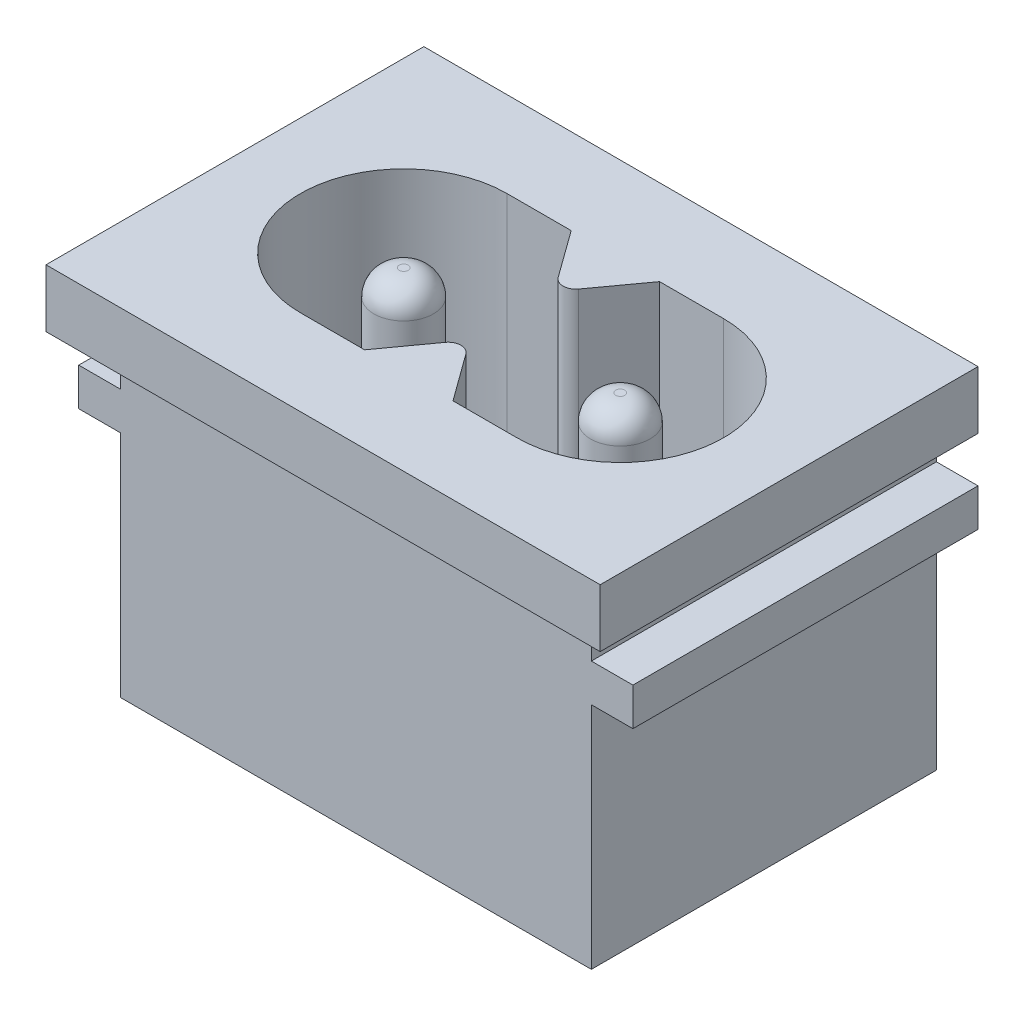
SolidWorks part; units mm, degrees
ref_plane "前视基准面" through (0, 0, 0) normal (0, 0, 1) x (1, 0, 0)
ref_plane "上视基准面" through (0, 0, 0) normal (0, 1, 0) x (1, 0, 0)
ref_plane "右视基准面" through (0, 0, 0) normal (1, 0, 0) x (0, 0, -1)
sketch "草图1" plane through (0, 0, 0) normal (0, 1, 0) x (1, 0, 0)
  line L0 (0, 0) -> (-50000, 0) construction
  line L1 (11, -7.5) -> (-11, -7.5)
  line L2 (11, -7.5) -> (11, 7.5)
  line L3 (11, 7.5) -> (-11, 7.5)
  line L4 (-11, -7.5) -> (-11, 7.5)
  line L5 (11, -7.5) -> (-11, 7.5) construction
  line L6 (11, 7.5) -> (-11, -7.5) construction
  line L7 (0, 0) -> (0, -50000) construction
  point P0 (0, 0)
  dimension "D1" = 22
  dimension "D2" = 15
extrude "凸台-拉伸1" add sketch "草图1" along normal blind 2.3
sketch "草图2" plane through (0, 0, 0) normal (0, -1, 0) x (1, 0, 0)
  line L0 (11, -7.5) -> (-11, -7.5) construction
  line L1 (-9.35, -7.5) -> (9.35, -7.5)
  line L2 (-9.35, -7.5) -> (-9.35, 6.2)
  line L3 (-9.35, 6.2) -> (9.35, 6.2)
  line L4 (9.35, -7.5) -> (9.35, 6.2)
  line L5 (0, 7.5) -> (0, -49992.5) construction
  line L6 (-11, 7.5) -> (11, 7.5) construction
  point P10 (0, 7.5)
  dimension "D1" = 13.7
  dimension "D2" = 18.7
  dimension "D3" = 9.35
extrude "凸台-拉伸2" add sketch "草图2" along normal blind 12.4
sketch "草图3" plane through (-9.35, 0, 0) normal (-1, 0, 0) x (0, 0, 1)
  line L0 (-7.5, -12.4) -> (-7.5, 0) construction
  line L1 (-7.5, -1.8) -> (6.2, -1.8)
  line L2 (-7.5, -1.8) -> (-7.5, -3.3)
  line L3 (-7.5, -3.3) -> (6.2, -3.3)
  line L4 (6.2, -1.8) -> (6.2, -3.3)
  line L5 (6.2, -12.4) -> (6.2, 0) construction
  line L7 (-7.5, 0) -> (7.5, 0) construction
  dimension "D1" = 1.5
  dimension "D2" = 1.8
extrude "凸台-拉伸3" add sketch "草图3" along normal up to surface (1.65 mm away) up to face at (-11, 1.15, 0)
sketch "草图4" plane through (9.35, 0, 0) normal (1, 0, 0) x (0, 0, -1)
  line L4 (-6.2, -3.3) -> (7.5, -3.3)
  line L5 (-6.2, -1.8) -> (-6.2, -3.3)
  line L6 (7.5, -1.8) -> (-6.2, -1.8)
  line L7 (7.5, -3.3) -> (7.5, -1.8)
  line L8 (-6.2, -3.3) -> (7.5, -3.3)
  line L9 (-6.2, -1.8) -> (-6.2, -3.3)
  line L10 (7.5, -1.8) -> (-6.2, -1.8)
  line L11 (7.5, -3.3) -> (7.5, -1.8)
  dimension "D1" = 0
extrude "凸台-拉伸4" add sketch "草图4" along normal up to surface (1.65 mm away) up to face at (11, 1.15, 0)
sketch "草图6" plane through (0, 2.3, 0) normal (0, 1, 0) x (1, 0, 0)
  line L0 (0, 7.5) -> (0, -7.5) construction
  line L1 (0.4055, -2.2378) -> (1.7575, -4.1)
  line L2 (-1.75, -4.1) -> (-0.4043, -2.2386)
  line L3 (-4.3, 4.1) -> (-1.75, 4.1)
  line L4 (1.7575, 4.1) -> (4.3, 4.1)
  line L5 (-10.3319, 0) -> (11.6681, 0) construction
  line L6 (1.7575, -4.1) -> (4.3, -4.1)
  line L7 (-4.3, -4.1) -> (-1.75, -4.1)
  line L8 (0, 2.1) -> (-5.3395, 2.1) construction
  line L9 (0, -1.8456) -> (-5.3395, -1.8456) construction
  line L10 (-1.75, 4.1) -> (-1.75, -49995.9) construction
  line L11 (1.75, 4.1) -> (1.75, -49995.9) construction
  line L12 (-1.75, 4.1) -> (-0.4043, 2.2386)
  line L13 (0.4055, 2.2378) -> (1.7575, 4.1)
  arc A0 (-4.3, 4.1) -> (-4.3, -4.1) centre (-4.3, 0) ccw
  arc A1 (4.3, 4.1) -> (4.3, -4.1) centre (4.3, 0) cw
  arc A2 (0.4055, -2.2378) -> (-0.4043, -2.2386) centre (0.0009, -2.5315) ccw
  arc A3 (0.4055, 2.2378) -> (-0.4043, 2.2386) centre (0.0009, 2.5315) cw
  point P26 (0, -1.6793)
  point P29 (0, 1.6793)
  dimension "D1" = 4.3
  dimension "D4" = 0.5
  dimension "D2" = 2.1
  dimension "D3" = 1.75
extrude "切除-拉伸1" cut sketch "草图6" against normal blind 10
sketch "草图5" plane through (0, -7.7, 0) normal (0, 1, 0) x (1, 0, 0)
  line L0 (0, 7.5) -> (0, -0.5223) construction
  line L2 (11, 0) -> (3.4823, 0) construction
  circle A0 centre (-4.3, 0) radius 1.18
  circle A1 centre (4.3, 0) radius 1.18
  dimension "D1" = 2.36
  dimension "D2" = 4.3
extrude "凸台-拉伸5" add sketch "草图5" along normal offset from surface (9.5 mm away) 0.5 up to face at (0.0014, 2.3, 0)
fillet "圆角6" radius 1 2 edges at (-4.3, 1.8, 1.18) (4.3, 1.8, 1.18)
sketch "草图7" plane through (0, 0, -7.5) normal (0, 0, -1) x (-1, 0, 0)
  line L0 (0, 2.3) -> (0, -49997.7) construction
  line L1 (-11, 2.3) -> (11, 2.3) construction
  line L2 (-9.35, -5.3) -> (9.35, -5.3) construction
  line L5 (-6.5, 2.3) -> (-6.5, -49997.7) construction
  line L6 (6.5, 2.3) -> (6.5, -49997.7) construction
  circle A0 centre (-6.5467, -5.3) radius 1.5
  circle A1 centre (6.5, -5.3) radius 1.5
  point P4 (0, 2.3)
  dimension "D3" = 3
  dimension "D1" = 7.6
  dimension "D2" = 6.5
extrude "凸台-拉伸6" [suppressed] add sketch "草图7" along normal blind 3
sketch "草图8" [suppressed] plane through (0, 0, -10.5) normal (0, 0, -1) x (-1, 0, 0)
  line L0 (6.5, -3.8) -> (6.5, -5.3) construction
  line L1 (-6.5467, -3.8) -> (-6.5467, -6.8) construction
  line L2 (-6.2967, -3.8) -> (-6.2967, -6.8)
  line L5 (0.0029, 2.3) -> (0.0029, -12.4) construction
  line L8 (-6.7967, -3.8) -> (-6.7967, -6.8)
  line L11 (-6.5467, -3.8) -> (-6.5467, -50003.8) construction
  line L12 (6.5525, -3.8) -> (6.5525, -6.8) construction
  line L13 (6.3025, -3.8) -> (6.3025, -6.8)
  line L14 (6.8025, -3.8) -> (6.8025, -6.8)
  circle A8 centre (-6.5467, -5.3) radius 1.5 construction
  arc A9 (-6.2967, -3.8) -> (-6.7967, -3.8) centre (-6.5467, -3.8) ccw
  arc A10 (-6.7967, -6.8) -> (-6.2967, -6.8) centre (-6.5467, -6.8) ccw
  arc A11 (6.3025, -3.8) -> (6.8025, -3.8) centre (6.5525, -3.8) cw
  arc A12 (6.8025, -6.8) -> (6.3025, -6.8) centre (6.5525, -6.8) cw
  point P6 (-6.5467, -5.3)
  point P14 (6.5525, -5.3)
  dimension "D1" = 0.5
extrude "切除-拉伸5" [suppressed] cut sketch "草图8" against normal blind 1.5
fillet "圆角7" [suppressed] radius 0.25
ref_axis "基准轴1" [suppressed] through (6.5467, -5.3, -10.5) along (0, 0, 1)
ref_plane "基准面1" [suppressed] through (0, -5.3, 0) normal (0, 1, 0) x (0, 0, 1)
ref_axis "基准轴2" [suppressed] through (-6.5, -5.3, -10.5) along (0, 0, 1)
sketch "草图9" [suppressed] plane through (0, -5.3, 0) normal (0, 1, 0) x (0, 0, 1)
  line L0 (-9.8632, 8.0467) -> (-10.5, 7.5638)
  line L1 (-7.5, 8.0467) -> (-10.5, 8.0467) construction
  line L2 (-10.5, 8.0467) -> (-10.5, 5.0467) construction
  line L3 (-10.5, 7.5638) -> (-10.5, 8.0467)
  line L4 (-10.5, 8.0467) -> (-9.8632, 8.0467)
  line L5 (-9.6992, 8.0467) -> (-9.6992, 7.8467)
  line L6 (-9.6992, 7.8467) -> (-7.5, 7.8467)
  line L7 (-7.5, 8.0467) -> (-7.5, 5.0467) construction
  line L8 (-7.5, 7.8467) -> (-7.5, 8.0467)
  line L9 (-7.5, 11) -> (-7.5, -11) construction
  line L10 (-7.5, 8.0467) -> (-9.6992, 8.0467)
  line L11 (-10.5, 5.0467) -> (-10.5, -5) construction
  line L12 (-10.5, 0.0234) -> (-50010.5, 0.0234) construction
  point P24 (-10.5, 0.0234)
  dimension "D1" = 0.2
revolve "切除-旋转1" [suppressed] cut sketch "草图9" angle 360 about axis through (6.5467, -5.3, -10.5) along (0, 0, 1)
sketch "草图10" [suppressed] plane through (0, -5.3, 0) normal (0, 1, 0) x (0, 0, 1)
  line L4 (-9.8632, 8.0372) -> (-10.5, 7.5638)
  line L5 (-9.8632, 8.0467) -> (-9.8632, 6.7967) construction
  line L13 (-10.5, 7.5638) -> (-10.5, 8.0372)
  line L14 (-10.5, 8.0372) -> (-9.8632, 8.0372)
  line L15 (-9.6992, 8.0467) -> (-7.5, 8.0467)
  line L16 (-7.5, 11) -> (-7.5, -11) construction
  line L17 (-7.5, 8.0467) -> (-7.5, 7.8467)
  line L18 (-7.5, 7.8467) -> (-9.6992, 7.8467)
  line L19 (-9.6992, 7.8467) -> (-9.6992, 8.0467)
  line L20 (-9.6992, 4.9553) -> (-9.6992, -5) construction
  line L21 (-7.5, -5) -> (-10.5, -5) construction
  line L22 (-9.6992, -0.0224) -> (-8.5376, -0.0224) construction
  line L23 (-7.5, -7.8914) -> (-9.6992, -7.8914)
  line L24 (-7.5, -8.0914) -> (-7.5, -7.8914)
  line L25 (-9.6992, -8.0914) -> (-7.5, -8.0914)
  line L26 (-9.6992, -7.8914) -> (-9.6992, -8.0914)
  line L27 (-10.5, -7.6085) -> (-10.5, -8.082)
  line L28 (-9.8632, -8.082) -> (-10.5, -7.6085)
  line L29 (-10.5, -8.082) -> (-9.8632, -8.082)
revolve "切除-旋转2" [suppressed] cut sketch "草图10" angle 360 about axis through (-6.5, -5.3, -10.5) along (0, 0, 1)
